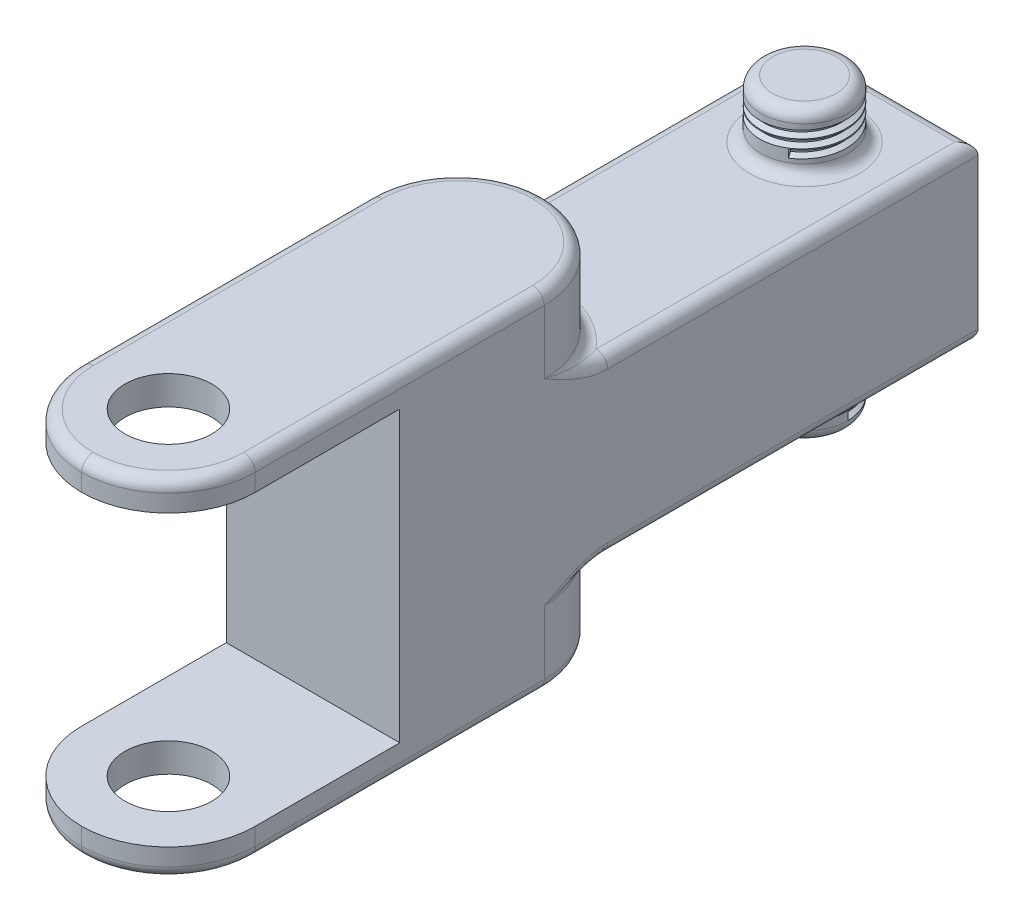
SolidWorks part; units mm, degrees
ref_plane "Front Plane" through (0, 0, 0) normal (0, 0, 1) x (1, 0, 0)
ref_plane "Top Plane" through (0, 0, 0) normal (0, 1, 0) x (1, 0, 0)
ref_plane "Right Plane" through (0, 0, 0) normal (1, 0, 0) x (0, 0, -1)
sketch "Esquisse1" plane through (0, 0, 0) normal (0, 0, 1) x (1, 0, 0)
  line L1 (-15, -15) -> (15, -15)
  line L2 (-15, -15) -> (-15, 15)
  line L3 (-15, 15) -> (15, 15)
  line L4 (15, -15) -> (15, 15)
  line L5 (-15, -15) -> (15, 15) construction
  line L6 (-15, 15) -> (15, -15) construction
  point P0 (0, 0)
  dimension "D1" = 30
  dimension "D2" = 30
extrude "Boss.-Extru.1" add sketch "Esquisse1" along normal blind 100
sketch "Esquisse2" plane through (0, 0, 100) normal (0, 0, 1) x (1, 0, 0)
  line L0 (15, 15) -> (-15, 15) construction
  line L1 (-15, -30) -> (15, -30)
  line L2 (-15, -30) -> (-15, 30)
  line L3 (-15, 30) -> (15, 30)
  line L4 (15, -30) -> (15, 30)
  line L5 (-15, -30) -> (15, 30) construction
  line L6 (-15, 30) -> (15, -30) construction
  point P0 (0, 0)
  line M6 (15, 15) -> (-15, 15)
  line M8 (-15, -15) -> (15, -15)
  dimension "D1" = 60
extrude "Boss.-Extru.2" add sketch "Esquisse2" along normal mid plane 80 contours L4 L3 L2 M6 | L1 L4 L2 M8 region at (0, -22.5, 100) region at (0, 22.5, 100)
fillet "Congé1" radius 15 8 edges at (-15, -22.5, 60) (15, -22.5, 60) (-15, 22.5, 60) (15, 22.5, 60) (-15, -22.5, 140) (-15, 22.5, 140) (15, -22.5, 140) (15, 22.5, 140)
sketch "Esquisse3" plane through (0, -30, 0) normal (0, -1, 0) x (1, 0, 0)
  circle A0 centre (0, 125) radius 7.5
  dimension "D1" = 15
extrude "Enlèv. mat.-Extru.1" cut sketch "Esquisse3" against normal through all
sketch "Esquisse4" plane through (0, 0, 0) normal (0, 1, 0) x (1, 0, 0)
  line L0 (0, 0) -> (0, -15) construction
  circle A0 centre (0, -15) radius 7.5
  dimension "D2" = 15
  dimension "D1" = 15
extrude "Boss.-Extru.3" add sketch "Esquisse4" along normal mid plane 50
fillet "Congé2" radius 2 26 edges at (15, 30, 100) (10.6066, 30, 135.6066) (-10.6066, 30, 135.6066) (-10.6066, 30, 64.3934) (10.6066, 30, 64.3934) (-15, 30, 100) (-10.6066, -30, 135.6066) (10.6066, -30, 135.6066) (15, -30, 100) (10.6066, -30, 64.3934) (-10.6066, -30, 64.3934) (-15, -30, 100) (0, -15, 0) (-10.6066, -15, 64.3934) (10.6066, -15, 64.3934) (15, -15, 37.5) (-15, -15, 37.5) (0, 15, 0) (15, 15, 37.5) (10.6066, 15, 64.3934) (-10.6066, 15, 64.3934) (-15, 15, 37.5) (0, 15, 7.5) (0, 25, 22.5) (0, -15, 22.5) (0, -25, 22.5)
sketch "Esquisse7" plane through (15, 0, 0) normal (1, 0, 0) x (0, 0, -1)
  line L0 (-100, 25) -> (-100, -25) construction
  line L1 (-100, -15) -> (-100, 15) construction
  line L3 (-100, 25) -> (-160.7024, 25)
  line L4 (-100, 25) -> (-100, -25)
  line L5 (-100, -25) -> (-160.7024, -25)
  line L6 (-160.7024, 25) -> (-160.7024, -25)
  point P4 (-100, 0)
  point P5 (-100, 0)
  dimension "D1" = 50
extrude "Enlèv. mat.-Extru.2" cut sketch "Esquisse7" against normal through all
thread "Filetage1" pitch 1.5 method cut profile "Profil de filetage1" start angle 0, offset 0, length 4, pitch 1.5, diameter 15
ref_plane "Plan1" through (7.5, -23, 15) normal (0, 0, 1) x (1, 0, 0)
sketch "Profil de filetage1" plane through (7.5, -23, 15) normal (0, 0, 1) x (1, 0, 0)
  line L0 (0, 0) -> (0, 1.5) construction
  line L11 (0, 0) -> (0, 1.3125)
  line L12 (0, 1.3125) -> (-0.8119, 0.8437)
  line L13 (-0.8119, 0.8437) -> (-0.8119, 0.4687)
  line L15 (-0.8119, 0.4687) -> (0, 0)
  line L17 (-0.8119, 0.6562) -> (0, 0.6562) construction
  point P2 (0, 0)
  dimension "Pitch" = 1.5
  dimension "Profile_Angle" = 60
  dimension "Profile_Land" = 0.375
  dimension "Profile_Height" = 0.8119
thread "Filetage2" pitch 1.5 method cut profile "Profil de filetage2" start angle 0, offset 0, length 4, pitch 1.5, diameter 15
ref_plane "Plan2" through (-7.5, 23, 15) normal (0, 0, 1) x (-1, 0, 0)
sketch "Profil de filetage2" plane through (-7.5, 23, 15) normal (0, 0, 1) x (-1, 0, 0)
  line L0 (0, 0) -> (0, 1.5) construction
  line L11 (0, 0) -> (0, 1.3125)
  line L12 (0, 1.3125) -> (-0.8119, 0.8437)
  line L13 (-0.8119, 0.8437) -> (-0.8119, 0.4687)
  line L15 (-0.8119, 0.4687) -> (0, 0)
  line L17 (-0.8119, 0.6562) -> (0, 0.6562) construction
  point P2 (0, 0)
  dimension "Pitch" = 1.5
  dimension "Profile_Angle" = 60
  dimension "Profile_Land" = 0.375
  dimension "Profile_Height" = 0.8119
